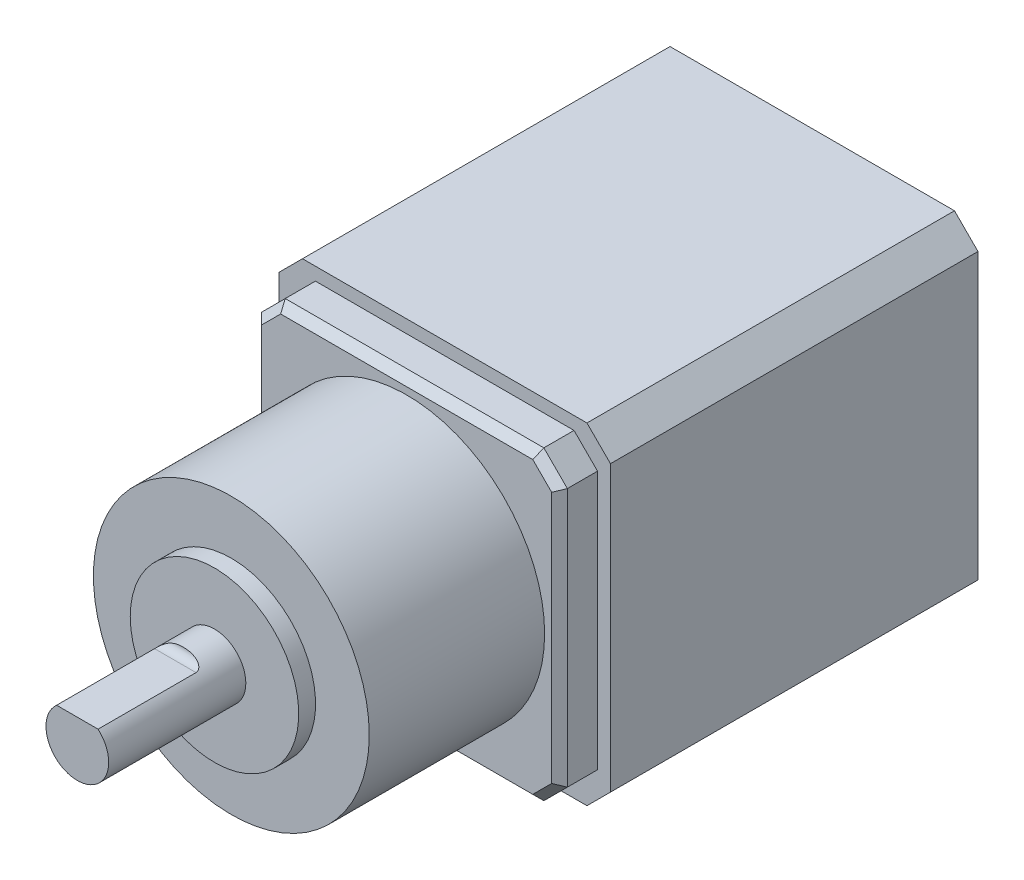
SolidWorks part; units mm, degrees
ref_plane "Front Plane" through (0, 0, 0) normal (0, 0, 1) x (1, 0, 0)
ref_plane "Top Plane" through (0, 0, 0) normal (0, 1, 0) x (1, 0, 0)
ref_plane "Right Plane" through (0, 0, 0) normal (1, 0, 0) x (0, 0, -1)
sketch "Sketch1" plane through (0, 0, 0) normal (0, 0, 1) x (1, 0, 0)
  line L1 (-21.15, -21.15) -> (21.15, -21.15)
  line L2 (-21.15, -21.15) -> (-21.15, 21.15)
  line L3 (-21.15, 21.15) -> (21.15, 21.15)
  line L4 (21.15, -21.15) -> (21.15, 21.15)
  line L5 (-21.15, -21.15) -> (21.15, 21.15) construction
  line L6 (-21.15, 21.15) -> (21.15, -21.15) construction
  point P0 (0, 0)
  dimension "D1" = 42.3
  dimension "D2" = 42.3
extrude "Boss-Extrude1" add sketch "Sketch1" along normal blind 46.9 contours L3 L4 L1 L2
sketch "Sketch2" plane through (0, 0, 46.9) normal (0, 0, 1) x (1, 0, 0)
  line L1 (-19.5, -19.5) -> (19.5, -19.5)
  line L2 (-19.5, -19.5) -> (-19.5, 19.5)
  line L3 (-19.5, 19.5) -> (19.5, 19.5)
  line L4 (19.5, -19.5) -> (19.5, 19.5)
  line L5 (-19.5, -19.5) -> (19.5, 19.5) construction
  line L6 (-19.5, 19.5) -> (19.5, -19.5) construction
  point P0 (0, 0)
  dimension "D1" = 39
extrude "Boss-Extrude2" add sketch "Sketch2" along normal blind 4.85
sketch "Sketch3" plane through (0, 0, 51.75) normal (0, 0, 1) x (1, 0, 0)
  circle A0 centre (0, 0) radius 17.6
  dimension "D1" = 35.2
extrude "Boss-Extrude3" add sketch "Sketch3" along normal blind 15.88
sketch "Sketch4" plane through (0, 0, 67.63) normal (0, 0, 1) x (1, 0, 0)
  circle A0 centre (0, 0) radius 17.6 construction
  circle A1 centre (0, 0) radius 17.6
extrude "Boss-Extrude4" add sketch "Sketch4" along normal blind 6.5
sketch "Sketch5" plane through (0, 0, 74.13) normal (0, 0, 1) x (1, 0, 0)
  circle A0 centre (0, 0) radius 10.75
  dimension "D1" = 21.5
extrude "Boss-Extrude5" add sketch "Sketch5" along normal blind 2.15
sketch "Sketch6" plane through (0, 0, 76.28) normal (0, 0, 1) x (1, 0, 0)
  circle A0 centre (0, 0) radius 4
  dimension "D1" = 8
extrude "Boss-Extrude6" add sketch "Sketch6" along normal blind 17.5
sketch "Sketch7" plane through (0, 0, 93.78) normal (0, 0, 1) x (1, 0, 0)
  line L0 (-2.6458, 3) -> (2.6458, 3)
  circle A0 centre (0, 0) radius 4 construction
  circle A2 centre (0, 0) radius 4
  circle M2 centre (0, 0) radius 4
  dimension "D1" = 7
extrude "Cut-Extrude1" cut sketch "Sketch7" against normal offset from surface (13.5 mm away) 4 contours L0 M2 region at (0, 3.4046, 93.78) up to face at (4, 0, 76.28)
chamfer "Chamfer1" distance 3 angle 45 8 edges at (-21.15, 21.15, 23.45) (-19.5, 19.5, 49.325) (-19.5, -19.5, 49.325) (-21.15, -21.15, 23.45) (21.15, -21.15, 23.45) (19.5, -19.5, 49.325) (19.5, 19.5, 49.325) (21.15, 21.15, 23.45)
chamfer "Chamfer2" distance 1 angle 45 8 edges at (18, 18, 51.75) (19.5, 0, 51.75) (18, -18, 51.75) (0, -19.5, 51.75) (-18, -18, 51.75) (-19.5, 0, 51.75) (-18, 18, 51.75) (0, 19.5, 51.75)
fillet "Fillet1" radius 1 1 edges at (0, 3, 80.28)
